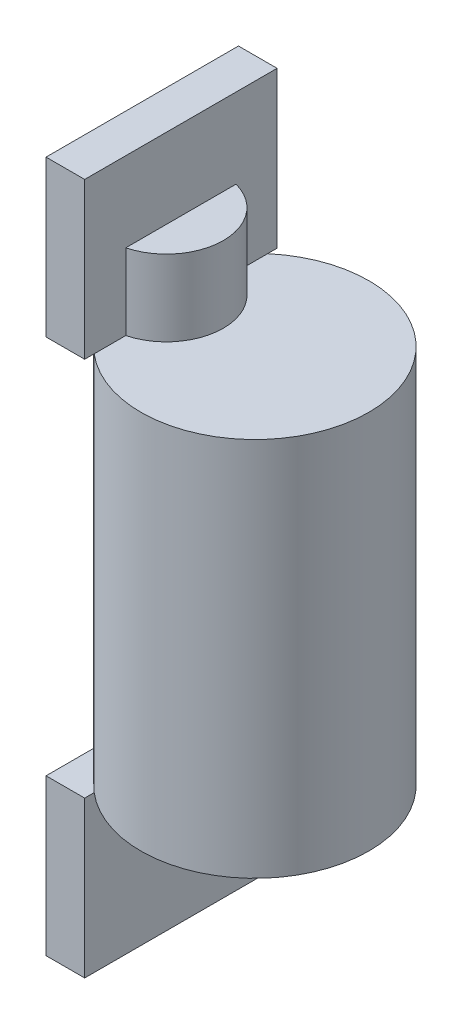
SolidWorks part; units mm, degrees
ref_plane "Спереди" through (0, 0, 0) normal (0, 0, 1) x (1, 0, 0)
ref_plane "Сверху" through (0, 0, 0) normal (0, 1, 0) x (1, 0, 0)
ref_plane "Справа" through (0, 0, 0) normal (1, 0, 0) x (0, 0, -1)
sketch "Эскиз1" plane through (0, 0, 0) normal (0, 1, 0) x (1, 0, 0)
  circle A0 centre (0, 0) radius 3
  dimension "D1" = 6
extrude "Бобышка-Вытянуть1" add sketch "Эскиз1" along normal blind 10
sketch "Эскиз5" plane through (0, 10, 0) normal (0, 1, 0) x (1, 0, 0)
  line L1 (-1.9472, 2.5317) -> (-2.9641, 2.5317)
  line L2 (-1.9472, 2.5317) -> (-1.9472, -2.5317)
  line L3 (-1.9472, -2.5317) -> (-2.9641, -2.5317)
  line L4 (-2.9641, 2.5317) -> (-2.9641, -2.5317)
  line L5 (-1.9472, 2.5317) -> (-2.9641, -2.5317) construction
  line L6 (-1.9472, -2.5317) -> (-2.9641, 2.5317) construction
  point P0 (-2.4557, 0)
extrude "Бобышка-Вытянуть3" add sketch "Эскиз5" along normal blind 4.1
ref_plane "Плоскость1" through (0, 5, 0) normal (0, 1, 0) x (1, 0, 0)
mirror "Зеркальное отражение1" about plane through (0, 5, 0) normal (0, 1, 0) of "Бобышка-Вытянуть3"
sketch "Эскиз3" plane through (0, 10, 0) normal (0, 1, 0) x (1, 0, 0)
  circle A0 centre (-2.3299, 0) radius 1.5
  dimension "D1" = 3
extrude "Бобышка-Вытянуть2" add sketch "Эскиз3" along normal blind 2
